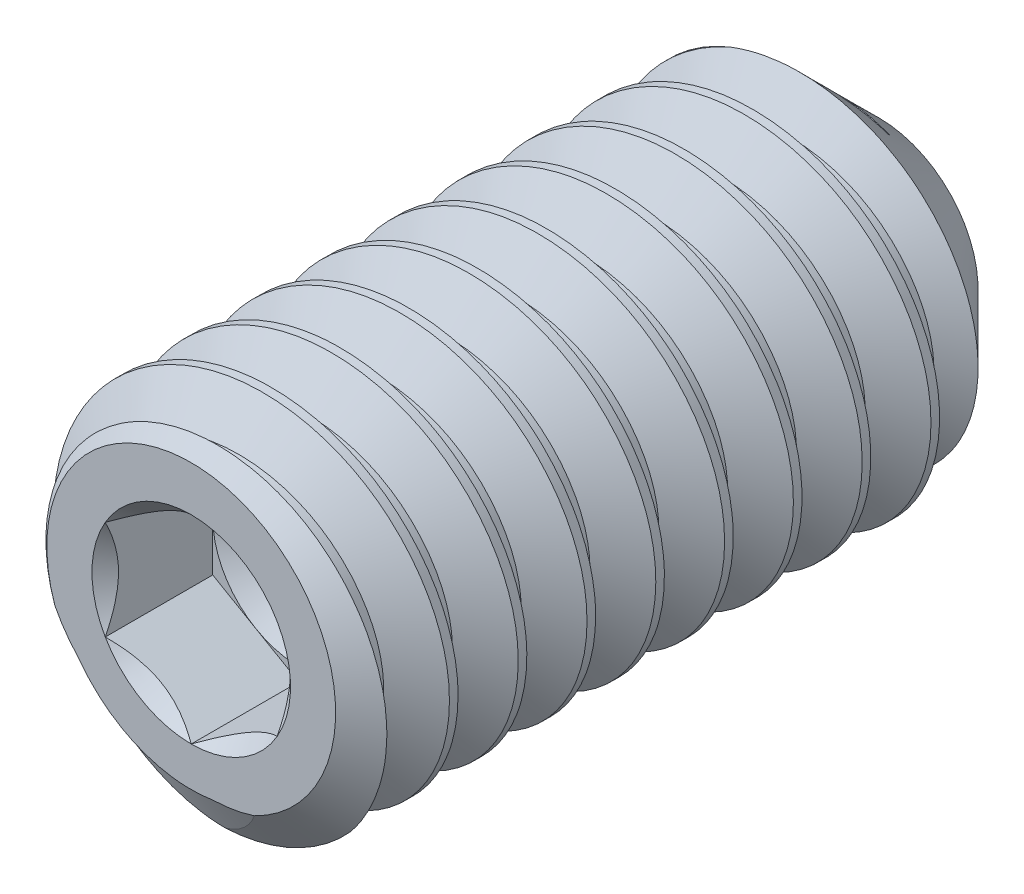
SolidWorks part; units mm, degrees
ref_plane "Front" through (0, 0, 0) normal (0, 0, 1) x (1, 0, 0)
ref_plane "Top" through (0, 0, 0) normal (0, 1, 0) x (1, 0, 0)
ref_plane "Right" through (0, 0, 0) normal (1, 0, 0) x (0, 0, -1)
sketch "Sketch22" plane through (0, 0, 0) normal (1, 0, 0) x (0, 0, -1)
  line L0 (-3.6259, 0) -> (-3.6259, 1.6662)
  line L1 (-3.6259, 1.6662) -> (-3.3342, 2.0828)
  line L2 (-3.3342, 2.0828) -> (3.3701, 2.0828)
  line L3 (3.3701, 2.0828) -> (4.3116, 1.1413)
  line L4 (4.3116, 1.1413) -> (3.6259, 0)
  line L5 (3.6259, 0) -> (-3.6259, 0)
  line L6 (3.6259, 0) -> (4.3116, 0) construction
  line L7 (4.3116, 0) -> (4.3116, 1.1413) construction
  line L8 (4.3116, -1.1413) -> (3.6259, 0) construction
  line L9 (-3.3342, -2.0828) -> (3.3701, -2.0828) construction
  dimension "Dia" = 4.1656
  dimension "Length" = 7.9375
  dimension "D3" = 35
  dimension "D5" = 118
  dimension "D6" = 45
  dimension "D7" = 3.3325
revolve "Revolve1" add sketch "Sketch22" angle 360 about L6
ref_plane "Plane1" through (0, 0, -4.3116) normal (0, 0, 1) x (1, 0, 0)
sketch "Sketch27" plane through (0, 0, -4.3116) normal (0, 0, 1) x (1, 0, 0)
  circle A0 centre (0, 0) radius 2.0828 construction
  circle A1 centre (0, 0) radius 2.0828
curve "Helix/Spiral1" pitch 0.7937 height 8.9853 radius 2.0828 centre (0, 0, -4.3116) axis (0, 0, 1) start towards (0, 1, 0)
sketch "Sketch28" plane through (0, 0, 0) normal (1, 0, 0) x (0, 0, -1)
  line L0 (4.3116, 2.0828) -> (5.0062, 2.0828)
  line L1 (5.0062, 2.0828) -> (4.7284, 1.6016)
  line L2 (4.7284, 1.6016) -> (4.5894, 1.6016)
  line L3 (4.5894, 1.6016) -> (4.3116, 2.0828)
  line L4 (4.4505, 1.8422) -> (4.8673, 1.8422) construction
  line L6 (-3.3342, 2.0828) -> (3.3701, 2.0828) construction
  line L7 (4.3116, 2.3089) -> (4.3116, -2.3089) construction
  dimension "D1" = 0.1389
  dimension "D2" = 0.6945
  dimension "D3" = 60
sweep "Cut-Sweep2" cut profiles "Sketch28" path "Helix/Spiral1"
sketch "Sketch23" plane through (0, 0, 3.6259) normal (0, 0, 1) x (1, 0, 0)
  line L1 (0, 1.1457) -> (-0.9922, 0.5728)
  line L2 (-0.9922, 0.5728) -> (-0.9922, -0.5728)
  line L3 (-0.9922, -0.5728) -> (0, -1.1457)
  line L4 (0, -1.1457) -> (0.9922, -0.5728)
  line L5 (0.9922, -0.5728) -> (0.9922, 0.5728)
  line L6 (0.9922, 0.5728) -> (0, 1.1457)
  circle A0 centre (0, 0) radius 0.9922 construction
  dimension "Hex" = 1.9844
extrude "Cut-Extrude10" cut sketch "Sketch23" against normal blind 1.2402
sketch "Sketch24" plane through (0, 0, 3.6259) normal (0, 0, 1) x (1, 0, 0)
  circle A0 centre (0, 0) radius 1.1457
extrude "Cut-Extrude11" cut sketch "Sketch24" against normal through all draft 45
sketch "Sketch26" plane through (0, 0, 2.3856) normal (0, 0, 1) x (1, 0, 0)
  circle A0 centre (0, 0) radius 0.9922 construction
  circle A1 centre (0, 0) radius 0.9922
extrude "Cut-Extrude12" cut sketch "Sketch26" against normal through all draft 60
sketch "Sketch30" plane through (0, 0, 0) normal (1, 0, 0) x (0, 0, -1)
  line L0 (-3.3342, 2.0828) -> (3.3701, 2.0828) construction
  line L1 (-3.6259, 0) -> (-3.6259, 1.6662) construction
  line L2 (4.3116, 0) -> (4.3116, 1.1413) construction
  line L3 (-3.3342, -2.0828) -> (3.3701, -2.0828) construction
  point P0 (-3.6259, 2.0828)
  point P1 (4.3116, 2.0828)
  point P2 (4.3116, -2.0828)
  point P11 (2.3273, -2.0828)
  dimension "D1" = 1.9844
sketch "Sketch31" plane through (0, 0, 0) normal (1, 0, 0) x (0, 0, -1)
  line L2 (3.6259, 0) -> (4.3116, -1.1413)
  line L3 (4.3116, 1.1413) -> (3.6259, 0)
equation "\"D7@Sketch22\"=\"Dia@Sketch22\"*.8"
equation "\"D1@Sketch28\" = \"D4@Helix/Spiral1\" * .175"
equation "\"D3@Helix/Spiral1\" = \"Length@Sketch22\" + \"D4@Helix/Spiral1\" + .01"
equation "\"D1@Sketch30\" = \"D4@Helix/Spiral1\" * 2.5"
equation "\"hex Depth@Cut-Extrude10\" = \"Hex@Sketch23\" * .625"
equation "\"D2@Sketch28\" = \"D4@Helix/Spiral1\" * .875"
